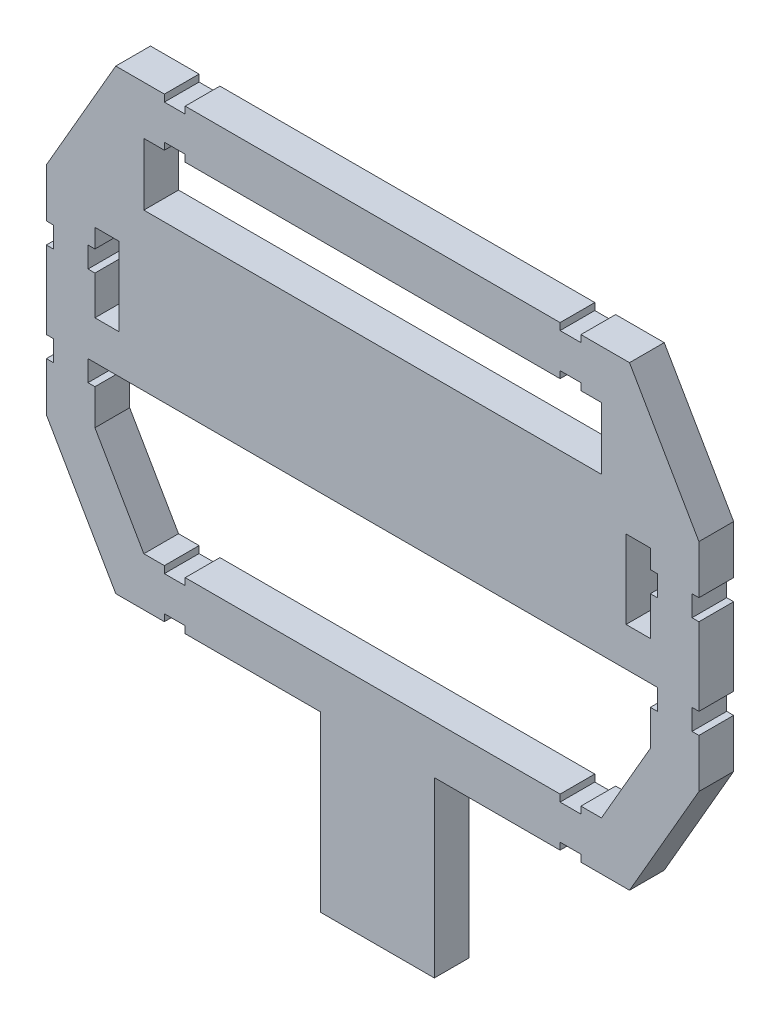
SolidWorks part; units mm, degrees
ref_plane "Plan de face" through (0, 0, 0) normal (0, 0, 1) x (1, 0, 0)
ref_plane "Plan de dessus" through (0, 0, 0) normal (0, 1, 0) x (1, 0, 0)
ref_plane "Plan de droite" through (0, 0, 0) normal (1, 0, 0) x (0, 0, -1)
sketch "Esquisse1" plane through (0, 0, 0) normal (0, 0, 1) x (1, 0, 0)
  line L0 (-12.5, -30.0222) -> (-12.5, -55.0222) construction
  line L1 (-32, -30.0222) -> (-32, -29.0222)
  line L2 (-32, -29.0222) -> (-35, -29.0222)
  line L3 (-35, -29.0222) -> (-35, -30.0222)
  line L4 (-35, -30.0222) -> (-42, -30.0222)
  line L5 (-42, -30.0222) -> (-52, -12.7017)
  line L6 (-52, -12.7017) -> (-52, -5.7017)
  line L7 (-52, -5.7017) -> (-51, -5.7017)
  line L8 (-51, -5.7017) -> (-51, -2.7017)
  line L9 (-51, -2.7017) -> (-52, -2.7017)
  line L10 (-52, -2.7017) -> (-52, 8.4752)
  line L11 (-5, -30.0222) -> (-5, 35.7957) construction
  line L12 (35, 2.8868) -> (-45, 2.8868) construction
  line L13 (-47, -21.362) -> (-5, 2.8868) construction
  line L14 (-45, 8.4752) -> (-45, -2.7017)
  line L15 (-45, -2.7017) -> (-46, -2.7017)
  line L16 (-46, -2.7017) -> (-46, -5.7017)
  line L17 (-46, -5.7017) -> (-45, -5.7017)
  line L18 (-45, -5.7017) -> (-45, -10.8261)
  line L19 (-45, -10.8261) -> (-37.9585, -23.0222)
  line L20 (-37.9585, -23.0222) -> (-35, -23.0222)
  line L21 (-35, -23.0222) -> (-35, -24.0222)
  line L22 (-35, -24.0222) -> (-32, -24.0222)
  line L23 (-32, -24.0222) -> (-32, -23.0222)
  line L24 (-32, -23.0222) -> (22, -23.0222)
  line L25 (-47, 27.1355) -> (-5, 2.8868) construction
  line L26 (-32, 28.7957) -> (22, 28.7957)
  line L27 (-32, 29.7957) -> (-32, 28.7957)
  line L28 (-35, 29.7957) -> (-32, 29.7957)
  line L29 (-35, 28.7957) -> (-35, 29.7957)
  line L30 (-37.9585, 28.7957) -> (-35, 28.7957)
  line L31 (-37.9585, 28.7957) -> (-37.9585, 19.8426)
  line L32 (-37.9585, 19.8426) -> (27.9585, 19.8426)
  line L33 (-46, 11.4752) -> (-45, 11.4752)
  line L34 (-46, 8.4752) -> (-46, 11.4752)
  line L35 (-45, 8.4752) -> (-46, 8.4752)
  line L36 (-51, 8.4752) -> (-52, 8.4752)
  line L37 (-51, 11.4752) -> (-51, 8.4752)
  line L38 (-52, 11.4752) -> (-51, 11.4752)
  line L39 (-52, 18.4752) -> (-52, 11.4752)
  line L40 (-42, 35.7957) -> (-52, 18.4752)
  line L41 (-35, 35.7957) -> (-42, 35.7957)
  line L42 (-35, 34.7957) -> (-35, 35.7957)
  line L43 (-32, 34.7957) -> (-35, 34.7957)
  line L44 (-32, 35.7957) -> (-32, 34.7957)
  line L45 (22, 35.7957) -> (-32, 35.7957)
  line L46 (37, 27.1355) -> (-5, 2.8868) construction
  line L47 (37, -21.362) -> (-5, 2.8868) construction
  line L48 (22, 35.7957) -> (22, 34.7957)
  line L49 (22, 34.7957) -> (25, 34.7957)
  line L50 (25, 34.7957) -> (25, 35.7957)
  line L51 (25, 35.7957) -> (32, 35.7957)
  line L52 (32, 35.7957) -> (42, 18.4752)
  line L53 (42, 18.4752) -> (42, 11.4752)
  line L54 (42, 11.4752) -> (41, 11.4752)
  line L55 (41, 11.4752) -> (41, 8.4752)
  line L56 (41, 8.4752) -> (42, 8.4752)
  line L57 (35, 8.4752) -> (36, 8.4752)
  line L58 (36, 8.4752) -> (36, 11.4752)
  line L59 (36, 11.4752) -> (35, 11.4752)
  line L60 (27.9585, 19.8426) -> (27.9585, 28.7957)
  line L61 (35, -2.7017) -> (-45, -2.7017)
  line L62 (27.9585, 28.7957) -> (25, 28.7957)
  line L63 (25, 28.7957) -> (25, 29.7957)
  line L64 (25, 29.7957) -> (22, 29.7957)
  line L65 (22, 29.7957) -> (22, 28.7957)
  line L66 (22, -24.0222) -> (22, -23.0222)
  line L67 (25, -24.0222) -> (22, -24.0222)
  line L68 (25, -23.0222) -> (25, -24.0222)
  line L69 (27.9585, -23.0222) -> (25, -23.0222)
  line L70 (35, -10.8261) -> (27.9585, -23.0222)
  line L71 (35, -5.7017) -> (35, -10.8261)
  line L72 (36, -5.7017) -> (35, -5.7017)
  line L73 (36, -2.7017) -> (36, -5.7017)
  line L74 (35, -2.7017) -> (36, -2.7017)
  line L75 (35, 8.4752) -> (35, -2.7017)
  line L76 (42, -2.7017) -> (42, 8.4752)
  line L77 (41, -2.7017) -> (42, -2.7017)
  line L78 (41, -5.7017) -> (41, -2.7017)
  line L79 (42, -5.7017) -> (41, -5.7017)
  line L80 (42, -12.7017) -> (42, -5.7017)
  line L81 (32, -30.0222) -> (42, -12.7017)
  line L82 (25, -30.0222) -> (32, -30.0222)
  line L83 (25, -29.0222) -> (25, -30.0222)
  line L84 (22, -29.0222) -> (25, -29.0222)
  line L85 (22, -30.0222) -> (22, -29.0222)
  line L86 (35, 2.8868) -> (31.5, 2.8868)
  line L87 (31.5, 2.8868) -> (31.5, 14.1772)
  line L88 (31.5, 14.1772) -> (35, 14.1772)
  line L89 (35, 14.1772) -> (35, 11.4752)
  line L90 (35, 11.4752) -> (34.9646, 11.6959)
  line L91 (-45, 2.8868) -> (-41.5, 2.8868)
  line L92 (-41.5, 2.8868) -> (-41.5, 14.1772)
  line L93 (-41.5, 14.1772) -> (-45, 14.1772)
  line L94 (-45, 14.1772) -> (-45, 11.4752)
  line L95 (-12.5, -30.0222) -> (-12.5, -55.0222)
  line L96 (-12.5, -55.0222) -> (3.8866, -55.0222)
  line L97 (3.8866, -55.0222) -> (3.8866, -30.0222)
  line L98 (3.8866, -30.0222) -> (22, -30.0222)
  line L99 (-12.5, -30.0222) -> (-32, -30.0222)
  line L101 (-12.5, -55.0222) -> (2.5, -55.0222) construction
  point P10 (-47, -21.362)
  point P41 (-52, 2.8868)
  point P73 (-5, 28.7957)
  point P74 (-5, -23.0222)
  point P75 (-5, -23.0222)
  point P94 (42, 2.8868)
  dimension "D1" = 1
  dimension "D2" = 3
  dimension "D3" = 7
  dimension "D4" = 3
  dimension "D5" = 7
  dimension "D6" = 60
  dimension "D7" = 90
  dimension "D8" = 1
  dimension "D9" = 1
  dimension "D10" = 1
  dimension "D11" = 7
  dimension "D13" = 7
  dimension "D14" = 20
  dimension "D15" = 30
  dimension "D16" = 2.702
  dimension "D17" = 3.5
extrude "Boss.-Extru.1" add sketch "Esquisse1" along normal blind 5 contours L85 L84 L83 L82 L81 L80 L79 L78 L77 L76 L56 L55 L54 L53 L52 L51 L50 L49 L48 L45 L44 L43 L42 L41 L40 L39 L38 L37 L36 L10 L9 L8 L7 L6 L5 L4 L3 L2 L1 L94 L93 L92 L91 L61 L86 L87 L88 region at (-4.9289, 0.8905, 0)
